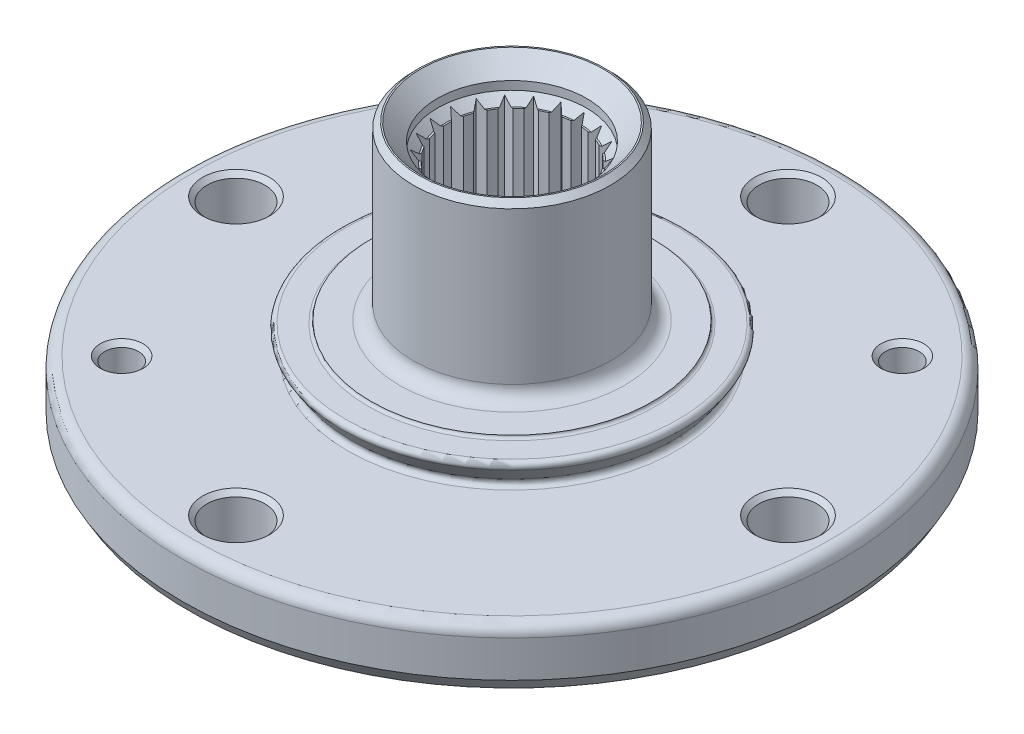
SolidWorks part; units mm, degrees
ref_plane "Plano frontal" through (0, 0, 0) normal (0, 0, 1) x (1, 0, 0)
ref_plane "Plano superior" through (0, 0, 0) normal (0, 1, 0) x (1, 0, 0)
ref_plane "Plano direito" through (0, 0, 0) normal (1, 0, 0) x (0, 0, -1)
sketch "Esboço1" plane through (0, 0, 0) normal (0, 0, 1) x (1, 0, 0)
  line L0 (24.5088, -37.3079) -> (24.5088, 43.9306) construction
  line L1 (35.9588, 35.2314) -> (35.9588, -3.2686)
  line L2 (35.9588, -3.2686) -> (47.2588, -3.2686)
  line L3 (47.2588, -3.2686) -> (47.2588, -8.7686)
  line L4 (47.2588, -8.7686) -> (51.0088, -20.7686)
  line L5 (51.0088, -20.7686) -> (53.5088, -20.7686)
  line L6 (53.5088, -20.7686) -> (53.5088, -10.2686)
  line L7 (53.5088, -10.2686) -> (54.0088, -10.2686)
  line L8 (54.0088, -10.2686) -> (54.0088, -5.2686)
  line L9 (54.0088, -5.2686) -> (83.0088, -5.2686)
  line L10 (83.0088, -5.2686) -> (83.0088, 5.2314)
  line L11 (83.0088, 5.2314) -> (52.183, 5.2314)
  line L12 (52.183, 5.2314) -> (55.5088, 10.2314)
  line L13 (55.5088, 10.2314) -> (49.5088, 10.2314)
  line L14 (49.5088, 10.2314) -> (49.5088, 10.7314)
  line L17 (49.5088, 10.7314) -> (42.0088, 10.7314)
  line L18 (42.0088, 10.7314) -> (42.0088, 41.2314)
  line L19 (42.0088, 41.2314) -> (37.7588, 41.2314)
  line L20 (37.7588, 41.2314) -> (37.7588, 35.2314)
  line L21 (37.7588, 35.2314) -> (35.9588, 35.2314)
  dimension "D1" = 11.45
  dimension "D2" = 13.25
  dimension "D3" = 17.5
  dimension "D4" = 25
  dimension "D5" = 31
  dimension "D6" = 58.5
  dimension "D7" = 29.5
  dimension "D8" = 29
  dimension "D9" = 26.5
  dimension "D10" = 22.75
  dimension "D11" = 6
  dimension "D12" = 17.5
  dimension "D13" = 5.5
  dimension "D14" = 5
  dimension "D15" = 15.5
  dimension "D16" = 10.5
  dimension "D17" = 36
  dimension "D18" = 31
  dimension "D19" = 30.5
revolve "Revolução1" add sketch "Esboço1" angle 360 about L0
sketch "Esboço2" plane through (0, -3.2686, 0) normal (0, -1, 0) x (1, 0, 0)
  line L0 (26.644, 11.0303) -> (28.6957, 10.4279)
  line L1 (23.4499, 11.185) -> (25.5883, 11.185)
  line L2 (24.5191, 12.8429) -> (23.4499, 11.185)
  line L3 (24.5191, 12.8429) -> (25.5883, 11.185)
  line L4 (28.1369, 12.3198) -> (26.644, 11.0303)
  line L5 (28.1369, 12.3198) -> (28.6957, 10.4279)
  line L6 (29.6651, 9.982) -> (31.464, 8.8259)
  line L7 (31.4609, 10.7986) -> (29.6651, 9.982)
  line L8 (31.4609, 10.7986) -> (31.464, 8.8259)
  line L9 (32.2685, 8.1249) -> (33.6688, 6.5089)
  line L10 (34.2216, 8.4026) -> (32.2685, 8.1249)
  line L11 (34.2216, 8.4026) -> (33.6688, 6.5089)
  line L12 (34.2432, 5.6097) -> (35.1315, 3.6646)
  line L13 (36.1954, 5.3258) -> (34.2432, 5.6097)
  line L14 (36.1954, 5.3258) -> (35.1315, 3.6646)
  line L15 (35.4293, 2.64) -> (35.7336, 0.5234)
  line L16 (37.2225, 1.8176) -> (35.4293, 2.64)
  line L17 (37.2225, 1.8176) -> (35.7336, 0.5234)
  line L18 (35.7307, -0.5436) -> (35.4264, -2.6602)
  line L19 (37.2196, -1.8379) -> (35.7307, -0.5436)
  line L20 (37.2196, -1.8379) -> (35.4264, -2.6602)
  line L21 (35.123, -3.6832) -> (34.2347, -5.6283)
  line L22 (36.1869, -5.3445) -> (35.123, -3.6832)
  line L23 (36.1869, -5.3445) -> (34.2347, -5.6283)
  line L24 (33.6554, -6.5244) -> (32.2551, -8.1404)
  line L25 (34.2082, -8.4181) -> (33.6554, -6.5244)
  line L26 (34.2082, -8.4181) -> (32.2551, -8.1404)
  line L27 (31.4468, -8.837) -> (29.6479, -9.993)
  line L28 (31.4436, -10.8097) -> (31.4468, -8.837)
  line L29 (31.4436, -10.8097) -> (29.6479, -9.993)
  line L30 (28.6761, -10.4336) -> (26.6243, -11.0361)
  line L31 (28.1173, -12.3256) -> (28.6761, -10.4336)
  line L32 (28.1173, -12.3256) -> (26.6243, -11.0361)
  line L33 (25.5678, -11.185) -> (23.4294, -11.185)
  line L34 (24.4986, -12.8429) -> (25.5678, -11.185)
  line L35 (24.4986, -12.8429) -> (23.4294, -11.185)
  line L36 (22.3737, -11.0303) -> (20.3219, -10.4279)
  line L37 (20.8807, -12.3198) -> (22.3737, -11.0303)
  line L38 (20.8807, -12.3198) -> (20.3219, -10.4279)
  line L39 (19.3526, -9.982) -> (17.5537, -8.8259)
  line L40 (17.5568, -10.7986) -> (19.3526, -9.982)
  line L41 (17.5568, -10.7986) -> (17.5537, -8.8259)
  line L42 (16.7492, -8.1249) -> (15.3489, -6.5089)
  line L43 (14.7961, -8.4026) -> (16.7492, -8.1249)
  line L44 (14.7961, -8.4026) -> (15.3489, -6.5089)
  line L45 (14.7744, -5.6097) -> (13.8861, -3.6646)
  line L46 (12.8222, -5.3258) -> (14.7744, -5.6097)
  line L47 (12.8222, -5.3258) -> (13.8861, -3.6646)
  line L48 (13.5883, -2.64) -> (13.284, -0.5234)
  line L49 (11.7952, -1.8176) -> (13.5883, -2.64)
  line L50 (11.7952, -1.8176) -> (13.284, -0.5234)
  line L51 (13.2869, 0.5436) -> (13.5912, 2.6602)
  line L52 (11.7981, 1.8379) -> (13.2869, 0.5436)
  line L53 (11.7981, 1.8379) -> (13.5912, 2.6602)
  line L54 (13.8947, 3.6832) -> (14.783, 5.6283)
  line L55 (12.8307, 5.3445) -> (13.8947, 3.6832)
  line L56 (12.8307, 5.3445) -> (14.783, 5.6283)
  line L57 (15.3623, 6.5244) -> (16.7626, 8.1404)
  line L58 (14.8095, 8.4181) -> (15.3623, 6.5244)
  line L59 (14.8095, 8.4181) -> (16.7626, 8.1404)
  line L60 (17.5709, 8.837) -> (19.3698, 9.993)
  line L61 (17.574, 10.8097) -> (17.5709, 8.837)
  line L62 (17.574, 10.8097) -> (19.3698, 9.993)
  line L63 (20.3416, 10.4336) -> (22.3933, 11.0361)
  line L64 (20.9004, 12.3256) -> (20.3416, 10.4336)
  line L65 (20.9004, 12.3256) -> (22.3933, 11.0361)
  dimension "D1" = 22
extrude "Corte-extrusão1" cut sketch "Esboço2" against normal through all
sketch "Esboço3" plane through (0, -5.2686, 0) normal (0, -1, 0) x (1, 0, 0)
  circle A0 centre (24.5088, 0) radius 49 construction
  circle A1 centre (24.5088, 49) radius 5.15
  circle A2 centre (59.1571, -34.6482) radius 3
  circle A3 centre (73.5088, 0) radius 5.15
  circle A5 centre (24.5088, -49) radius 5.15
  circle A6 centre (-10.1394, 34.6482) radius 3
  circle A7 centre (-24.4912, 0) radius 5.15
  circle A9 centre (59.1571, 34.6482) radius 5.15 [skipped]
  circle A10 centre (-10.1394, -34.6482) radius 5.15 [skipped]
  circle A11 centre (-10.1394, 34.6482) radius 5.15 [skipped]
  circle A12 centre (59.1571, -34.6482) radius 5.15 [skipped]
  point P8 (0, 0)
  point P9 (-49, 24.5088)
  dimension "D1" = 98
  dimension "D2" = 8
  dimension "D3" = 6
  dimension "D4" = 6
extrude "Corte-extrusão2" cut sketch "Esboço3" against normal through all
chamfer "Chanfro1" distance 0.8 angle 45 12 edges at (24.5088, 5.2314, -43.85) (24.5088, -5.2686, -54.15) (24.5088, -5.2686, 43.85) (24.5088, 5.2314, 54.15) (73.5088, 5.2314, 5.15) (73.5088, -5.2686, -5.15) (59.1571, 5.2314, -31.6482) (59.1571, -5.2686, -37.6482) (-24.4912, -5.2686, -5.15) (-24.4912, 5.2314, 5.15) (-10.1394, 5.2314, 37.6482) (-10.1394, -5.2686, 31.6482)
chamfer "Chanfro2" distance 2 angle 30 1 edges at (24.5088, -5.2686, -58.5) first distance on face at (24.5088, 5.2314, -58.5)
fillet "Filete1" radius 2 1 edges at (24.5088, -5.2686, -29.5)
fillet "Filete2" radius 1 1 edges at (24.5088, -10.2686, -29)
chamfer "Chanfro3" distance 1 angle 30 1 edges at (24.5088, -20.7686, -29) first distance on face at (24.5088, -11.1346, 29)
fillet "Filete3" radius 1.5 1 edges at (24.5088, -3.2686, -22.75)
fillet "Filete4" radius 0.5 1 edges at (24.5088, -8.7686, -22.75)
fillet "Filete5" radius 2 1 edges at (24.5088, 5.2314, -58.5)
fillet "Filete6" radius 0.8 1 edges at (24.5088, 5.2314, -27.6742)
fillet "Filete7" radius 0.8 1 edges at (24.5088, 10.2314, -31)
fillet "Filete8" radius 2.5 1 edges at (24.5088, 10.7314, -17.5)
fillet "Filete9" radius 0.5 1 edges at (24.5088, 10.2314, -25)
chamfer "Chanfro4" distance 3 angle 45 1 edges at (24.5088, 41.2314, -13.25)
chamfer "Chanfro5" distance 1 angle 45 1 edges at (24.5088, 41.2314, -17.5)
chamfer "Chanfro6" distance 1.5 angle 45 1 edges at (24.5088, 35.2314, -13.25)
